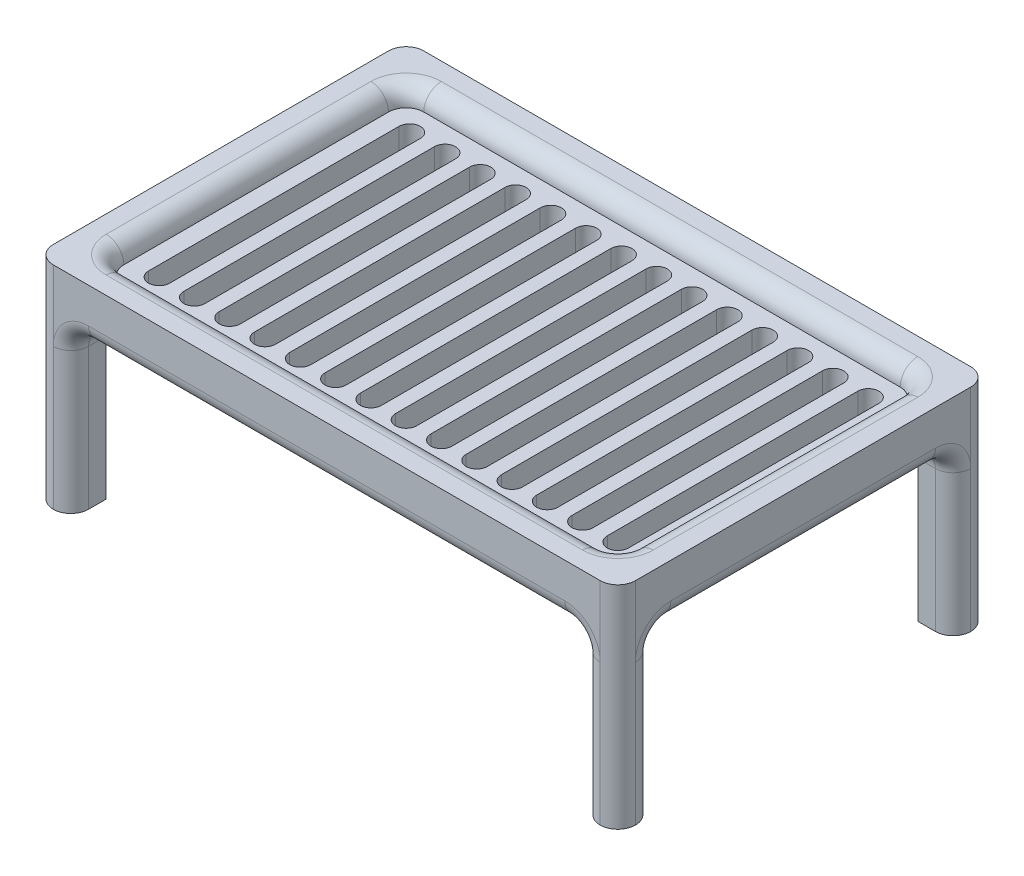
SolidWorks part; units mm, degrees
ref_plane "Front Plane" through (0, 0, 0) normal (0, 0, 1) x (1, 0, 0)
ref_plane "Top Plane" through (0, 0, 0) normal (0, 1, 0) x (1, 0, 0)
ref_plane "Right Plane" through (0, 0, 0) normal (1, 0, 0) x (0, 0, -1)
sketch "Sketch2" plane through (0, 0, 0) normal (0, 1, 0) x (1, 0, 0)
  line L0 (0, 0) -> (145, 0)
  line L1 (145, 0) -> (145, 85)
  line L2 (145, 85) -> (0, 85)
  line L3 (0, 85) -> (0, 0)
  dimension "D1" = 145
  dimension "D2" = 85
extrude "Boss-Extrude1" add sketch "Sketch2" along normal blind 10
sketch "Sketch3" plane through (0, 0, 0) normal (0, -1, 0) x (1, 0, 0)
  line L0 (0, 0) -> (145, 0) construction
  line L1 (0, -85) -> (0, 0) construction
  line L2 (145, -85) -> (0, -85) construction
  line L3 (145, 0) -> (145, -85) construction
  line L18 (155, 10) -> (-10, 10)
  line L19 (155, -95) -> (155, 10)
  line L20 (-10, 10) -> (-10, -95)
  line L21 (-10, -95) -> (155, -95)
  line L22 (155, 10) -> (-10, 10)
  line L23 (155, -95) -> (155, 10)
  line L24 (-10, 10) -> (-10, -95)
  line L25 (-10, -95) -> (155, -95)
  circle A0 centre (20, -20) radius 7.5
  circle A1 centre (125, -20) radius 7.5
  circle A2 centre (20, -65) radius 7.5
  circle A3 centre (125, -65) radius 7.5
  point P10 (0, 0)
  point P12 (8.2611, -29.5949)
  point P18 (0, 0)
  line M9 (0, 0) -> (0, -85)
  line M10 (0, -85) -> (145, -85)
  line M11 (145, -85) -> (145, 0)
  line M12 (145, 0) -> (0, 0)
  dimension "D1" = 20
  dimension "D4" = 20
  dimension "D5" = 20
  dimension "D7" = 15
  dimension "D2" = 20
  dimension "D3" = 20
  dimension "D6" = 20
  dimension "D8" = 10
extrude "Boss-Extrude3" add sketch "Sketch3" against normal blind 15 contours L24 L25 L23 L22 M9 M12 M11 M10
sketch "Sketch7" plane through (0, 0, 0) normal (0, -1, 0) x (1, 0, 0)
  line L1 (-10, 10) -> (0, 10)
  line L2 (-10, 10) -> (-10, 0)
  line L3 (-10, 0) -> (0, 0)
  line L4 (0, 10) -> (0, 0)
  line L5 (-10, -95) -> (0, -95)
  line L6 (-10, -95) -> (-10, -85)
  line L7 (-10, -85) -> (0, -85)
  line L8 (0, -95) -> (0, -85)
  line L9 (155, 10) -> (145, 10)
  line L10 (155, 10) -> (155, 0)
  line L11 (155, 0) -> (145, 0)
  line L12 (145, 10) -> (145, 0)
  line L13 (155, -95) -> (145, -95)
  line L14 (155, -95) -> (155, -85)
  line L15 (155, -85) -> (145, -85)
  line L16 (145, -95) -> (145, -85)
  line M9 (-10, 10) -> (-10, -95)
  line M10 (-10, -95) -> (155, -95)
  line M11 (155, -95) -> (155, 10)
  line M12 (155, 10) -> (-10, 10)
  dimension "D1" = 10
  dimension "D2" = 10
  dimension "D3" = 10
  dimension "D4" = 10
  dimension "D5" = 10
  dimension "D6" = 10
  dimension "D7" = 10
  dimension "D8" = 10
extrude "Boss-Extrude4" add sketch "Sketch7" along normal blind 45 contours L4 L3 M12 M9 | L12 L11 M12 M11 | L16 L15 M10 M11 | L8 L7 M10 M9
fillet "Fillet2" radius 5 8 edges at (0, 12.5, -85) (145, 12.5, -85) (145, 12.5, 0) (0, 12.5, 0) (-10, -15, 10) (-10, -15, -95) (155, -15, -95) (155, -15, 10)
sketch "Sketch8" plane through (0, 10, 0) normal (0, 1, 0) x (1, 0, 0)
  line L0 (8, 78) -> (8, 7) construction
  line L1 (11, 78) -> (11, 7)
  line L2 (5, 78) -> (5, 7)
  line L3 (0, 80) -> (0, 5) construction
  line L4 (140, 85) -> (5, 85) construction
  line L5 (15, 78) -> (15, 7)
  line L6 (140, 0) -> (5, 0) construction
  line L7 (21, 78) -> (21, 7)
  line L8 (18, 78) -> (18, 7) construction
  line L9 (25, 78) -> (25, 7)
  line L10 (31, 78) -> (31, 7)
  line L11 (28, 78) -> (28, 7) construction
  line L12 (35, 78) -> (35, 7)
  line L13 (41, 78) -> (41, 7)
  line L14 (38, 78) -> (38, 7) construction
  line L15 (45, 78) -> (45, 7)
  line L16 (51, 78) -> (51, 7)
  line L17 (48, 78) -> (48, 7) construction
  line L18 (55, 78) -> (55, 7)
  line L19 (61, 78) -> (61, 7)
  line L20 (58, 78) -> (58, 7) construction
  line L21 (65, 78) -> (65, 7)
  line L22 (71, 78) -> (71, 7)
  line L23 (68, 78) -> (68, 7) construction
  line L24 (75, 78) -> (75, 7)
  line L25 (81, 78) -> (81, 7)
  line L26 (78, 78) -> (78, 7) construction
  line L27 (85, 78) -> (85, 7)
  line L28 (91, 78) -> (91, 7)
  line L29 (88, 78) -> (88, 7) construction
  line L30 (95, 78) -> (95, 7)
  line L31 (101, 78) -> (101, 7)
  line L32 (98, 78) -> (98, 7) construction
  line L33 (105, 78) -> (105, 7)
  line L34 (111, 78) -> (111, 7)
  line L35 (108, 78) -> (108, 7) construction
  line L36 (115, 78) -> (115, 7)
  line L37 (121, 78) -> (121, 7)
  line L38 (118, 78) -> (118, 7) construction
  line L39 (125, 78) -> (125, 7)
  line L40 (131, 78) -> (131, 7)
  line L41 (128, 78) -> (128, 7) construction
  line L42 (135, 78) -> (135, 7)
  line L43 (141, 78) -> (141, 7)
  line L44 (138, 78) -> (138, 7) construction
  arc A0 (11, 78) -> (5, 78) centre (8, 78) ccw
  arc A1 (5, 7) -> (11, 7) centre (8, 7) ccw
  arc A2 (21, 78) -> (15, 78) centre (18, 78) ccw
  arc A3 (15, 7) -> (21, 7) centre (18, 7) ccw
  arc A4 (31, 78) -> (25, 78) centre (28, 78) ccw
  arc A5 (25, 7) -> (31, 7) centre (28, 7) ccw
  arc A6 (41, 78) -> (35, 78) centre (38, 78) ccw
  arc A7 (35, 7) -> (41, 7) centre (38, 7) ccw
  arc A8 (51, 78) -> (45, 78) centre (48, 78) ccw
  arc A9 (45, 7) -> (51, 7) centre (48, 7) ccw
  arc A10 (61, 78) -> (55, 78) centre (58, 78) ccw
  arc A11 (55, 7) -> (61, 7) centre (58, 7) ccw
  arc A12 (71, 78) -> (65, 78) centre (68, 78) ccw
  arc A13 (65, 7) -> (71, 7) centre (68, 7) ccw
  arc A14 (81, 78) -> (75, 78) centre (78, 78) ccw
  arc A15 (75, 7) -> (81, 7) centre (78, 7) ccw
  arc A16 (91, 78) -> (85, 78) centre (88, 78) ccw
  arc A17 (85, 7) -> (91, 7) centre (88, 7) ccw
  arc A18 (101, 78) -> (95, 78) centre (98, 78) ccw
  arc A19 (95, 7) -> (101, 7) centre (98, 7) ccw
  arc A20 (111, 78) -> (105, 78) centre (108, 78) ccw
  arc A21 (105, 7) -> (111, 7) centre (108, 7) ccw
  arc A22 (121, 78) -> (115, 78) centre (118, 78) ccw
  arc A23 (115, 7) -> (121, 7) centre (118, 7) ccw
  arc A24 (131, 78) -> (125, 78) centre (128, 78) ccw
  arc A25 (125, 7) -> (131, 7) centre (128, 7) ccw
  arc A26 (141, 78) -> (135, 78) centre (138, 78) ccw
  arc A27 (135, 7) -> (141, 7) centre (138, 7) ccw
  point P2 (8, 42.5)
  point P9 (18, 42.5)
  point P23 (28, 42.5)
  point P30 (38, 42.5)
  point P37 (48, 42.5)
  point P44 (58, 42.5)
  point P51 (68, 42.5)
  point P58 (78, 42.5)
  point P65 (88, 42.5)
  point P72 (98, 42.5)
  point P79 (108, 42.5)
  point P86 (118, 42.5)
  point P93 (128, 42.5)
  point P100 (138, 42.5)
  dimension "D1" = 3
  dimension "D2" = 5
  dimension "D3" = 7
  dimension "D4" = 7
  dimension "D5" = 14
extrude "Cut-Extrude2" cut sketch "Sketch8" against normal blind 45
fillet "Fillet3" radius 5 8 edges at (1.4645, 15, -83.5355) (0, 15, -42.5) (1.4645, 15, -1.4645) (72.5, 15, 0) (143.5355, 15, -1.4645) (145, 15, -42.5) (143.5355, 15, -83.5355) (72.5, 15, -85)
fillet "Fillet6" radius 5 20 edges at (-10, -22.5, -85) (0, -22.5, -95) (0, -22.5, 10) (-10, -22.5, 0) (155, -22.5, -85) (145, -22.5, -95) (155, -22.5, 0) (145, -22.5, 10) (-5, 0, -85) (0, 0, -90) (0, 0, 5) (-5, 0, 0) (150, 0, -85) (145, 0, -90) (150, 0, 0) (145, 0, 5) (-10, 0, -42.5) (72.5, 0, 10) (155, 0, -42.5) (72.5, 0, -95)
